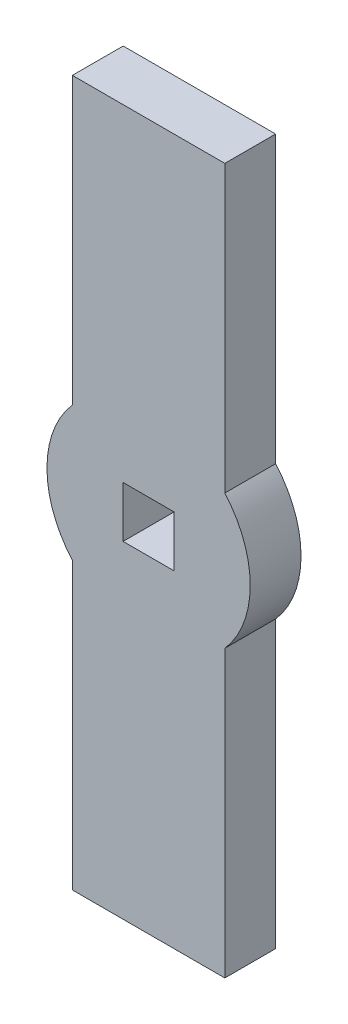
SolidWorks part; units mm, degrees
ref_plane "Front Plane" through (0, 0, 0) normal (0, 0, 1) x (1, 0, 0)
ref_plane "Top Plane" through (0, 0, 0) normal (0, 1, 0) x (1, 0, 0)
ref_plane "Right Plane" through (0, 0, 0) normal (1, 0, 0) x (0, 0, -1)
sketch "Sketch2" plane through (0, 0, 0) normal (0, 0, 1) x (1, 0, 0)
  line L0 (0, -167.7125) -> (0, 44.0843) construction
  line L5 (-9.525, 8.4003) -> (-9.525, 44.0843)
  line L6 (-9.525, 44.0843) -> (9.525, 44.0843)
  line L7 (9.525, 44.0843) -> (9.525, 8.4003)
  line L8 (-74.2931, 0) -> (71.2723, 0) construction
  line L9 (9.525, -44.0843) -> (9.525, -8.4003)
  line L15 (-9.525, -44.0843) -> (9.525, -44.0843)
  line L16 (-9.525, -8.4003) -> (-9.525, -44.0843)
  circle A1 centre (0, 0) radius 2.032
  circle A4 centre (0, 0) radius 12.7 construction
  arc A5 (-9.525, 8.4003) -> (-9.525, -8.4003) centre (0, 0) ccw
  arc A9 (9.525, -8.4003) -> (9.525, 8.4003) centre (0, 0) ccw
  point P5 (9.525, 8.4003)
  dimension "D4" = 4.064
  dimension "D1" = 25.4
  dimension "D5" = 35.684
  dimension "D6" = 19.05
extrude "Boss-Extrude1" add sketch "Sketch2" along normal blind 6.35
sketch "Sketch3" plane through (0, 0, 0) normal (0, 0, -1) x (-1, 0, 0)
  line L1 (-3.19, 3.19) -> (3.19, 3.19)
  line L2 (-3.19, 3.19) -> (-3.19, -3.19)
  line L3 (-3.19, -3.19) -> (3.19, -3.19)
  line L4 (3.19, 3.19) -> (3.19, -3.19)
  line L5 (-3.19, 3.19) -> (3.19, -3.19) construction
  line L6 (-3.19, -3.19) -> (3.19, 3.19) construction
  point P0 (0, 0)
  dimension "D1" = 6.38
  dimension "D2" = 6.38
extrude "Cut-Extrude1" cut sketch "Sketch3" against normal through all
